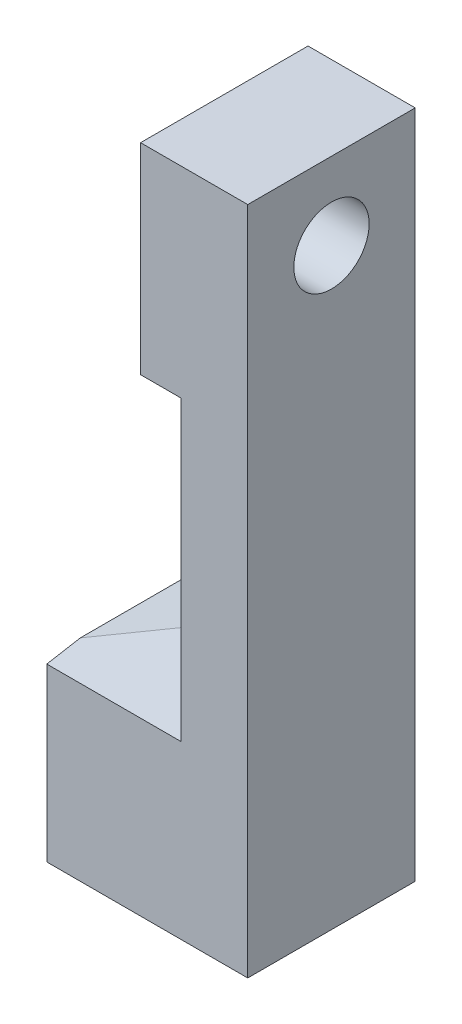
SolidWorks part; units mm, degrees
ref_plane "Front Plane" through (0, 0, 0) normal (0, 0, 1) x (1, 0, 0)
ref_plane "Top Plane" through (0, 0, 0) normal (0, 1, 0) x (1, 0, 0)
ref_plane "Right Plane" through (0, 0, 0) normal (1, 0, 0) x (0, 0, -1)
sketch "Sketch1" plane through (0, 0, 0) normal (1, 0, 0) x (0, 0, -1)
  line L1 (-7.9375, 31.75) -> (7.9375, 31.75)
  line L2 (-7.9375, 31.75) -> (-7.9375, -31.75)
  line L3 (-7.9375, -31.75) -> (7.9375, -31.75)
  line L4 (7.9375, 31.75) -> (7.9375, -31.75)
  line L5 (-7.9375, 31.75) -> (7.9375, -31.75) construction
  line L6 (-7.9375, -31.75) -> (7.9375, 31.75) construction
  point P0 (0, 0)
  dimension "D1" = 63.5
  dimension "D2" = 15.875
extrude "Boss-Extrude1" add sketch "Sketch1" along normal blind 6.35
sketch "Sketch2" plane through (0, 0, 0) normal (-1, 0, 0) x (0, 0, 1)
  line L0 (-7.9375, -31.75) -> (-7.9375, 31.75) construction
  line L1 (7.9375, 31.75) -> (-7.9375, 31.75)
  line L2 (7.9375, 31.75) -> (7.9375, 12.7)
  line L4 (-7.9375, 31.75) -> (-7.9375, 15.4992)
  line L5 (-7.9375, 15.4992) -> (7.9375, 12.7)
  line L6 (-7.9375, -31.75) -> (-7.9375, 31.75) construction
  dimension "D1" = 80
  dimension "D2" = 19.05
extrude "Boss-Extrude2" add sketch "Sketch2" along normal blind 3.81
sketch "Sketch3" plane through (0, 0, 0) normal (-1, 0, 0) x (0, 0, 1)
  line L0 (-7.9375, -31.75) -> (-7.9375, 15.4992) construction
  line L1 (-7.9375, -12.7) -> (-7.9375, -31.75)
  line L2 (-7.9375, -31.75) -> (7.9375, -31.75)
  line L3 (7.9375, -31.75) -> (7.9375, -15.4992)
  line L4 (7.9375, 12.7) -> (7.9375, -31.75) construction
  line L5 (7.9375, -15.4992) -> (-7.9375, -12.7)
  dimension "D1" = 80
  dimension "D2" = 19.05
extrude "Boss-Extrude3" add sketch "Sketch3" along normal blind 12.7
sketch "Sketch6" plane through (0, 0, -7.9375) normal (0, 0, -1) x (-1, 0, 0)
  line L0 (0, -12.7) -> (12.7, -12.7)
  line L2 (12.7, -12.7) -> (12.7, -14.9394)
  line L3 (12.7, -14.9394) -> (0, -12.7)
  line L7 (12.7, -15.4992) -> (12.7, -12.7) construction
  point P2 (0, -15.4992)
  point P3 (0, 0)
  point P4 (0, -15.4992)
  point P6 (0, 0)
  point P7 (16.0983, -15.5386)
  dimension "D1" = 10
extrude "Cut-Extrude1" cut sketch "Sketch6" against normal through all
hole_wizard "1/4 Clearance Hole1" positions "Sketch4" profile "Sketch5" hole size "1/4" standard "ANSI Inch" end condition through all
sketch "Sketch4" plane through (6.35, 0, 0) normal (1, 0, 0) x (0, 0, -1)
  line L1 (7.9375, 15.4992) -> (-7.9375, 12.7) construction
  point P0 (0, 24.4163)
  dimension "D1" = 10.16
sketch "Sketch5" plane through (6.35, 24.4163, 0) normal (0, 1, 0) x (0, 0, -1)
  line L0 (0, 0) -> (0, 19.05)
  line L1 (0, 19.05) -> (3.5712, 19.05)
  line L2 (3.5712, 19.05) -> (3.5712, 0)
  line L5 (3.5712, 0) -> (0, 0)
  line L11 (0, -6.35) -> (0, 107.95) construction
  dimension "Thru Hole Dia." = 7.1425
  dimension "Thru Hole Depth" = 19.05
